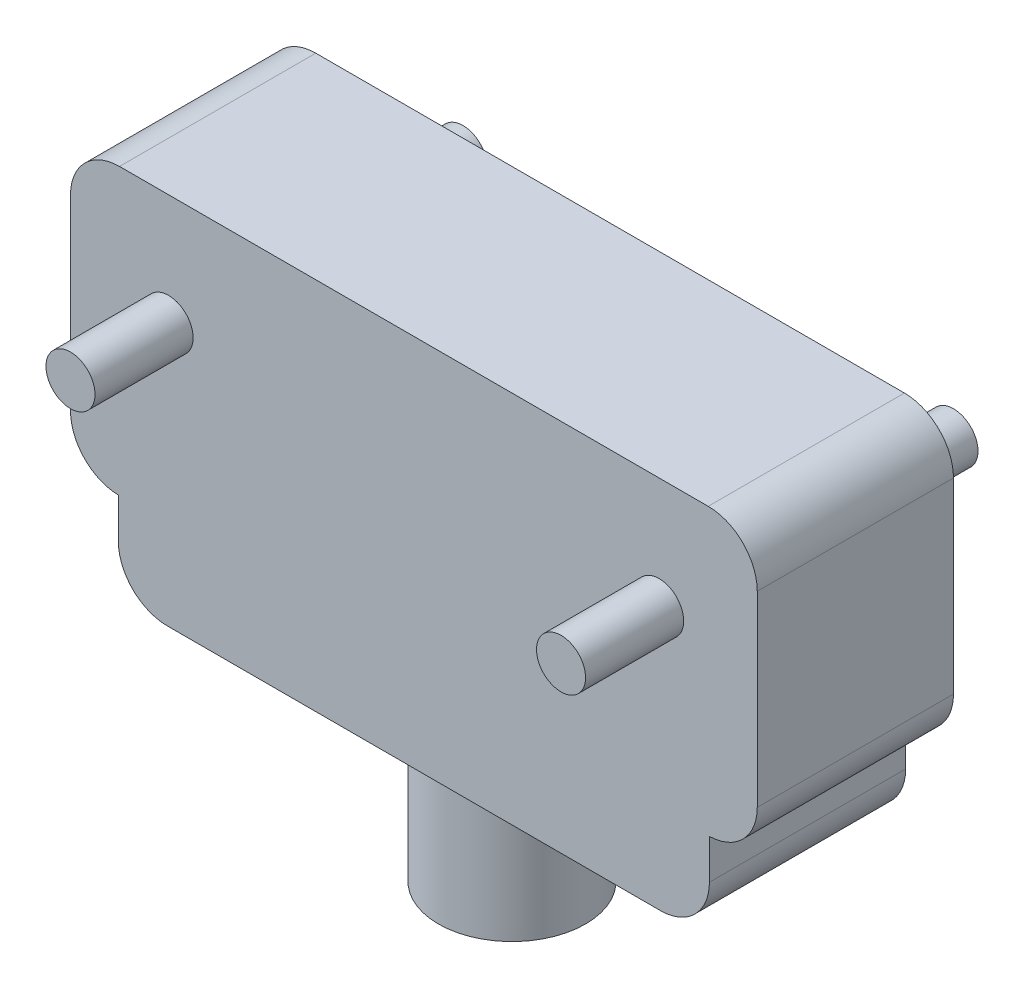
SolidWorks part; units mm, degrees
ref_plane "Front Plane" through (0, 0, 0) normal (0, 0, 1) x (1, 0, 0)
ref_plane "Top Plane" through (0, 0, 0) normal (0, 1, 0) x (1, 0, 0)
ref_plane "Right Plane" through (0, 0, 0) normal (1, 0, 0) x (0, 0, -1)
sketch "Sketch1" plane through (0, 0, 0) normal (0, 0, 1) x (1, 0, 0)
  circle A0 centre (90.07, -85.0656) radius 2.5 construction
  circle A1 centre (40.07, -85.0656) radius 2.5 construction
  circle A2 centre (90.07, -85.0656) radius 2.5
  circle A3 centre (40.07, -85.0656) radius 2.5
extrude "Boss-Extrude1" add sketch "Sketch1" against normal blind 10
sketch "Sketch2" plane through (0, 0, 0) normal (0, 0, 1) x (1, 0, 0)
  line L0 (40.07, -85.0656) -> (40.07, -95.6885) construction
  line L1 (30.07, -73.6824) -> (100.07, -73.6824)
  line L2 (30.07, -73.6824) -> (30.07, -102.7559)
  line L4 (100.07, -73.6824) -> (100.07, -102.7559)
  line L5 (90.07, -85.0656) -> (90.07, -95.6885) construction
  line L6 (30.07, -102.7559) -> (34.9457, -102.7559)
  line L7 (34.9457, -102.7559) -> (34.9457, -111.806)
  line L8 (34.9457, -111.806) -> (95.1943, -111.806)
  line L9 (65.07, -118.6824) -> (65.07, -89.6118) construction
  line L10 (95.1943, -102.7559) -> (95.1943, -111.806)
  line L11 (100.07, -102.7559) -> (95.1943, -102.7559)
  point P17 (65.07, -111.806)
  dimension "D1" = 10
  dimension "D2" = 10
  dimension "D3" = 60
extrude "Boss-Extrude2" add sketch "Sketch2" along normal blind 20
fillet "Fillet1" radius 5 6 edges at (100.07, -73.6824, 10) (100.07, -102.7559, 10) (95.1943, -111.806, 10) (34.9457, -111.806, 10) (30.07, -102.7559, 10) (30.07, -73.6824, 10)
sketch "Sketch4" plane through (0, -111.806, 0) normal (0, -1, 0) x (1, 0, 0)
  circle A0 centre (65.07, 10) radius 7.5
  dimension "D1" = 15
extrude "Boss-Extrude3" add sketch "Sketch4" along normal blind 15
sketch "Sketch5" plane through (0, 0, 20) normal (0, 0, 1) x (1, 0, 0)
  circle A0 centre (90.07, -85.0656) radius 2.5 construction
  circle A1 centre (40.07, -85.0656) radius 2.5 construction
  circle A2 centre (90.07, -85.0656) radius 2.5
  circle A3 centre (40.07, -85.0656) radius 2.5
extrude "Boss-Extrude4" add sketch "Sketch5" along normal blind 10
